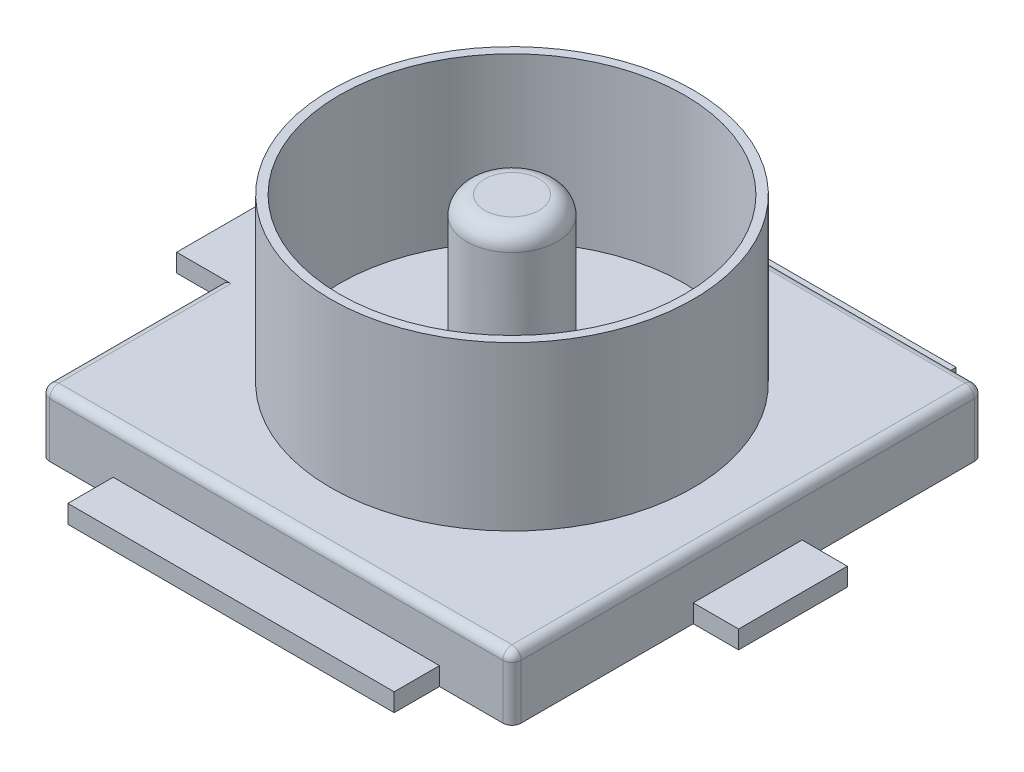
SolidWorks part; units mm, degrees
ref_plane "前视基准面" through (0, 0, 0) normal (0, 0, 1) x (1, 0, 0)
ref_plane "上视基准面" through (0, 0, 0) normal (0, 1, 0) x (1, 0, 0)
ref_plane "右视基准面" through (0, 0, 0) normal (1, 0, 0) x (0, 0, -1)
sketch "草图1" plane through (0, 0, 0) normal (0, 1, 0) x (1, 0, 0)
  line L1 (0, 0) -> (2.6, 0)
  line L2 (0, 0) -> (0, 2.6)
  line L3 (0, 2.6) -> (2.6, 2.6)
  line L4 (2.6, 0) -> (2.6, 2.6)
  dimension "D1" = 2.6
  dimension "D2" = 2.6
extrude "凸台-拉伸1" add sketch "草图1" along normal blind 0.35
sketch "草图2" plane through (0, 0.35, 0) normal (0, 1, 0) x (1, 0, 0)
  line L0 (-0.1456, 1.3) -> (2.7385, 1.3) construction
  line L1 (1.3, 2.6883) -> (1.3, -0.1349) construction
  line L3 (2.6, 2.6) -> (0, 2.6) construction
  line L4 (0, 0) -> (2.6, 0) construction
  line L5 (0, 2.6) -> (0, 0) construction
  line L6 (2.6, 0) -> (2.6, 2.6) construction
  circle A0 centre (1.3, 1.3) radius 1
  circle A1 centre (1.3, 1.3) radius 0.9515
  circle A2 centre (1.3, 1.3) radius 0.25
  dimension "D1" = 2
  dimension "D2" = 1.9031
  dimension "D3" = 0.5
extrude "凸台-拉伸2" add sketch "草图2" along normal blind 0.9 contours A2 | A0 A1 region at (0.3283, 0.35, -1.3) region at (1.3, 0.35, -1.3)
sketch "草图3" plane through (2.6, 0, 0) normal (1, 0, 0) x (0, 0, -1)
  line L0 (1.3, -0.1045) -> (1.3, 0.4824) construction
  line L1 (2.6, 0.35) -> (2.6, 0) construction
  line L2 (0, 0.35) -> (0, 0) construction
  line L3 (0, 0) -> (2.6, 0) construction
  line L4 (1, 0) -> (1.6, 0)
  line L5 (1, 0) -> (1, 0.1)
  line L6 (1, 0.1) -> (1.6, 0.1)
  line L7 (1.6, 0) -> (1.6, 0.1)
  dimension "D1" = 0.6
  dimension "D2" = 0.1
extrude "凸台-拉伸3" add sketch "草图3" along normal blind 0.25
sketch "草图4" plane through (0, 0, 0) normal (0, 0, 1) x (1, 0, 0)
  line L0 (1.3, -0.1504) -> (1.3, 0.499) construction
  line L1 (0, 0) -> (2.6, 0) construction
  line L2 (0.4, 0) -> (2.2, 0)
  line L3 (0.4, 0) -> (0.4, 0.1)
  line L4 (0.4, 0.1) -> (2.2, 0.1)
  line L5 (2.2, 0) -> (2.2, 0.1)
  line L6 (2.6, 0.35) -> (2.6, 0) construction
  line L7 (0, 0.35) -> (0, 0) construction
  dimension "D1" = 1.8
  dimension "D2" = 0.1
extrude "凸台-拉伸4" add sketch "草图4" along normal blind 0.25
sketch "草图5" plane through (0, 0, -2.6) normal (0, 0, -1) x (-1, 0, 0)
  line L0 (-1.3, -0.117) -> (-1.3, 0.4565) construction
  line L1 (-2.6, 0) -> (0, 0) construction
  line L2 (-2.2, 0) -> (-0.4, 0)
  line L3 (-2.2, 0) -> (-2.2, 0.1)
  line L4 (-2.2, 0.1) -> (-0.4, 0.1)
  line L5 (-0.4, 0) -> (-0.4, 0.1)
  line L6 (-2.6, 0.35) -> (-2.6, 0) construction
  line L7 (0, 0.35) -> (0, 0) construction
  dimension "D1" = 1.8
  dimension "D2" = 0.1
extrude "凸台-拉伸5" add sketch "草图5" along normal blind 0.25
sketch "草图6" plane through (0, 0, 0) normal (-1, 0, 0) x (0, 0, 1)
  line L0 (-1.3, -0.1194) -> (-1.3, 0.4517) construction
  line L1 (-2.6, 0.35) -> (0, 0.35) construction
  line L2 (-1.6, 0.35) -> (-1, 0.35)
  line L3 (-1.6, 0.35) -> (-1.6, 0.25)
  line L4 (-1.6, 0.25) -> (-1, 0.25)
  line L5 (-1, 0.35) -> (-1, 0.25)
  line L6 (-2.6, 0.35) -> (-2.6, 0) construction
  line L7 (0, 0.35) -> (0, 0) construction
  dimension "D1" = 0.6
  dimension "D2" = 0.1
extrude "凸台-拉伸6" add sketch "草图6" along normal blind 0.25
fillet "圆角1" radius 0.1 1 edges at (1.3, 1.25, -1.05)
fillet "圆角2" radius 0.05 5 edges at (1.3, 0.35, -2.6) (1.3, 0.35, 0) (2.6, 0.35, -1.3)
fillet "圆角3" radius 0.05 8 edges at (0.0146, 0.3354, -2.5854) (0.0146, 0.3354, -0.0146) (2.5854, 0.3354, -0.0146) (2.5854, 0.3354, -2.5854) (0, 0.15, -2.6) (0, 0.15, 0) (2.6, 0.15, 0) (2.6, 0.15, -2.6)
